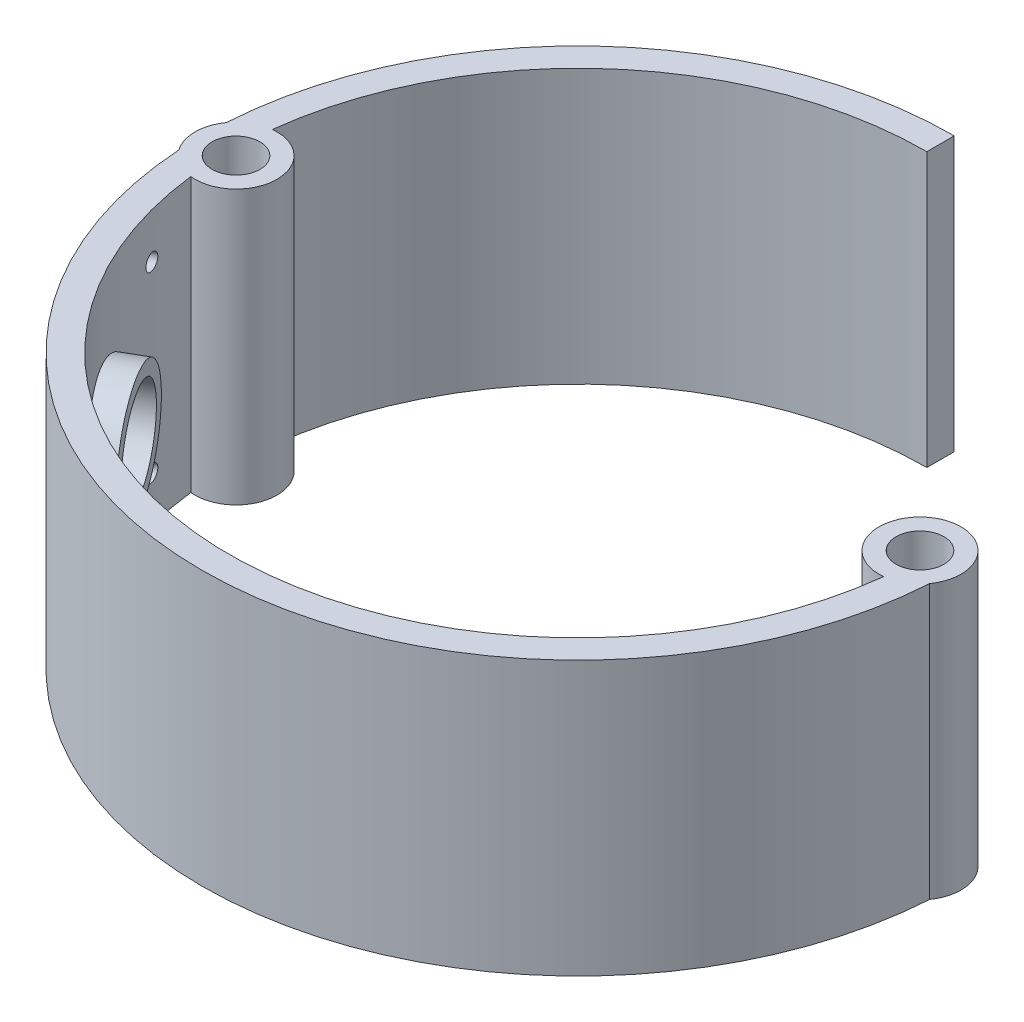
SolidWorks part; units mm, degrees
ref_plane "Front Plane" through (0, 0, 0) normal (0, 0, 1) x (1, 0, 0)
ref_plane "Top Plane" through (0, 0, 0) normal (0, 1, 0) x (1, 0, 0)
ref_plane "Right Plane" through (0, 0, 0) normal (1, 0, 0) x (0, 0, -1)
sketch "Sketch1" plane through (0, 0, 0) normal (0, 1, 0) x (1, 0, 0)
  line L0 (0, 0) -> (63.5, 0)
  line L1 (63.5, 0) -> (63.5, 69.85)
  circle A0 centre (0, 0) radius 4.445
  circle A1 centre (0, 0) radius 7.62
  circle A2 centre (127, 0) radius 4.445
  circle A3 centre (127, 0) radius 7.62
  circle A4 centre (63.5, 0) radius 69.85
  circle A5 centre (63.5, 0) radius 64.77
  dimension "D1" = 8.89
  dimension "D2" = 15.24
  dimension "D5" = 139.7
  dimension "D4" = 63.5
  dimension "D6" = 5.08
  dimension "D3" = 2
extrude "Boss-Extrude2" add sketch "Sketch1" along normal blind 50.8 contours A5 L1 A4 A1 | A4 A1 | A5 A1 A4 A0 | A1 A5 A0 L0 | A0 A5 A1 L0 | A5 A1 A4 A3 | A3 A5 A2 | A5 A3 A4 A2 | A4 A3 region at (3.5082, 0, -4.1182) region at (3.5082, 0, 4.1182) region at (-4.6063, 0, 0) region at (-4.3402, 0, -7.3967) region at (63.5, 0, 66.3101) region at (-6.8341, 0, 0) region at (128.1577, 0, 5.9541) region at (119.5557, 0, 0) region at (133.8341, 0, 0)
ref_axis "Axis1" through (63.5, 50.8, 0) along (0, -1, 0)
ref_plane "Plane1" through (47.625, 0, -27.4963) normal (-0.866, 0, 0.5) x (0, -1, 0)
sketch "Sketch2" plane through (47.625, 0, -27.4963) normal (-0.866, 0, 0.5) x (0, -1, 0)
  line L0 (-50.8, 31.75) -> (0, 31.75) construction
  circle A0 centre (-25.4, 31.75) radius 8.255
  dimension "D1" = 16.51
  dimension "D2" = 25.4
extrude "Cut-Extrude1" cut sketch "Sketch2" along normal through all
sketch "Sketch3" plane through (47.625, 0, -27.4963) normal (-0.866, 0, 0.5) x (0, -1, 0)
  circle A4 centre (-42.4, 14.75) radius 1.5
  circle A5 centre (-8.4, 14.75) radius 1.5
  circle A6 centre (-8.4, 48.75) radius 1.5
  circle A7 centre (-42.4, 48.75) radius 1.5
extrude "Cut-Extrude2" cut sketch "Sketch3" along normal through all
ref_plane "Plane2" through (-9.5673, 0, 5.5237) normal (-0.866, 0, 0.5) x (0, -1, 0)
sketch "Sketch4" plane through (-9.5673, 0, 5.5237) normal (-0.866, 0, 0.5) x (0, -1, 0)
  circle A0 centre (-25.4, 31.75) radius 8.89
  circle A1 centre (-25.4, 31.75) radius 11.43
  dimension "D1" = 17.78
  dimension "D2" = 2.54
extrude "Boss-Extrude3" add sketch "Sketch4" against normal blind 6.35
